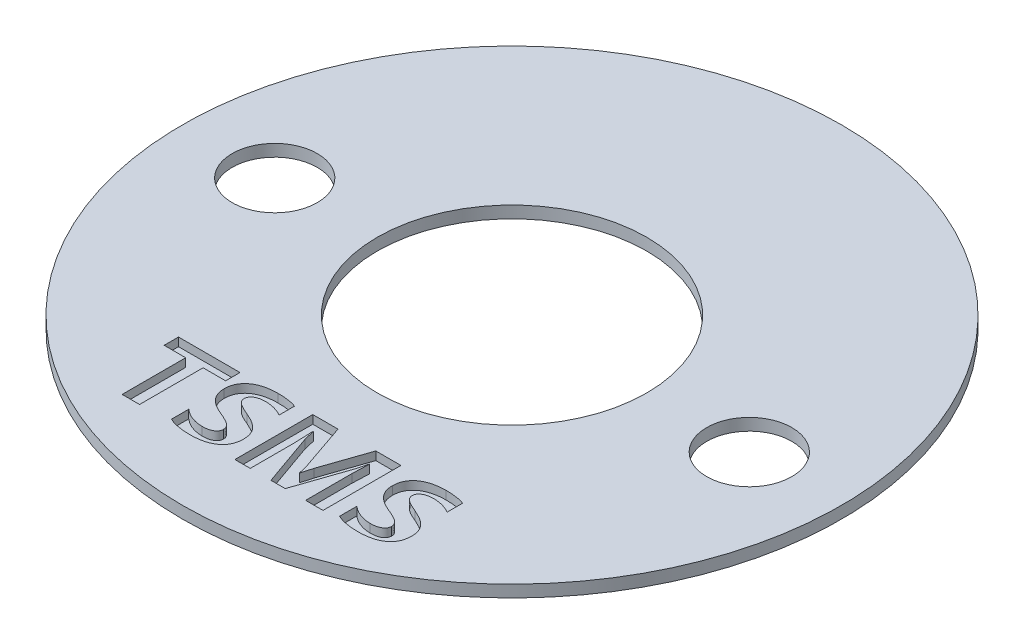
SolidWorks part; units mm, degrees
material "ABS"
ref_plane "Front Plane" through (0, 0, 0) normal (0, 0, 1) x (1, 0, 0)
ref_plane "Top Plane" through (0, 0, 0) normal (0, 1, 0) x (1, 0, 0)
ref_plane "Right Plane" through (0, 0, 0) normal (1, 0, 0) x (0, 0, -1)
sketch "Sketch1" plane through (0, 0, 0) normal (0, 1, 0) x (1, 0, 0)
  circle A0 centre (0, 0) radius 27.5
  dimension "D1" = 55
extrude "Boss-Extrude1" add sketch "Sketch1" along normal blind 1
sketch "Sketch4" plane through (0, 0, 0) normal (0, -1, 0) x (1, 0, 0)
  line L0 (-19.8, 0) -> (19.8, 0) construction
  circle A4 centre (-19.8, 0) radius 3.55
  circle A5 centre (0, 0) radius 11.25
  circle A6 centre (19.8, 0) radius 3.55
  point P1 (17.376, -12.225)
  point P4 (0, 0)
  point P6 (0, 0)
  dimension "D1" = 7.1
  dimension "D2" = 22.5
  dimension "D3" = 39.6
extrude "Cut-Extrude2" cut sketch "Sketch4" against normal through all
sketch "Sketch2" plane through (0, 1, 0) normal (0, 1, 0) x (1, 0, 0)
  line L0 (-12.5, -22) -> (12.5, -22) construction
  line L1 (0, 0) -> (0, -22) construction
  text T0 "TSMS" font "Nirmala UI" height 6.5
  point P3 (0, 0)
  point P4 (13.5275, -17.6909)
  dimension "D1" = 25
  dimension "D2" = 22
extrude "Cut-Extrude1" cut sketch "Sketch2" against normal offset from surface (0.7 mm away) 0.3 up to face at (-19.8, 0, -3.55)
